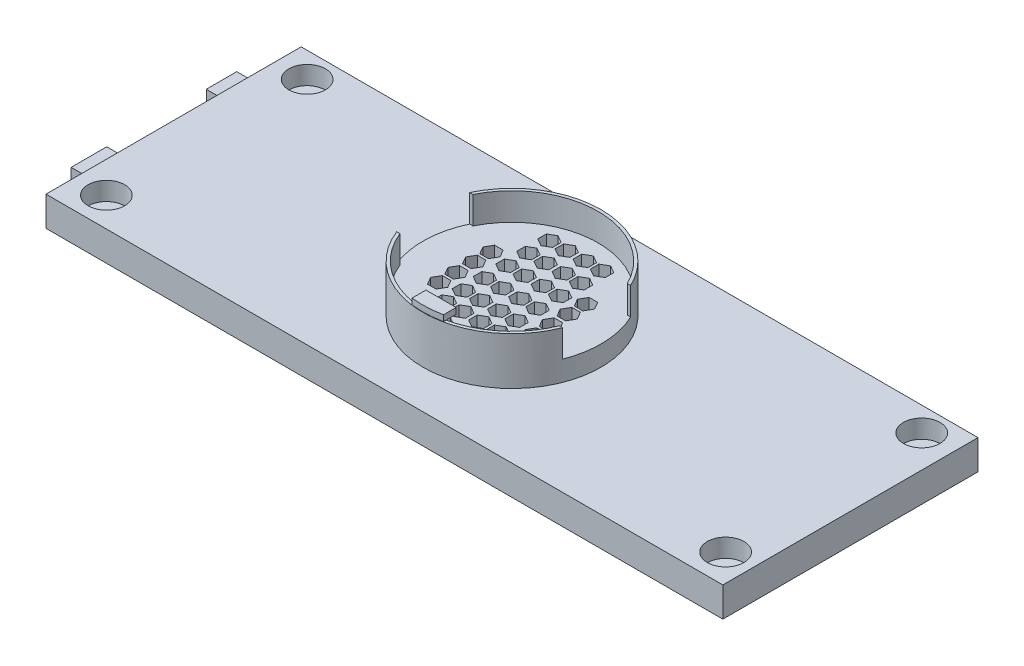
SolidWorks part; units mm, degrees
ref_plane "Front Plane" through (0, 0, 0) normal (0, 0, 1) x (1, 0, 0)
ref_plane "Top Plane" through (0, 0, 0) normal (0, 1, 0) x (1, 0, 0)
ref_plane "Right Plane" through (0, 0, 0) normal (1, 0, 0) x (0, 0, -1)
sketch "Sketch1" plane through (0, 0, 0) normal (0, 1, 0) x (1, 0, 0)
  line L1 (57, -21.4874) -> (-57, -21.4874)
  line L2 (57, -21.4874) -> (57, 21.4874)
  line L3 (57, 21.4874) -> (-57, 21.4874)
  line L4 (-57, -21.4874) -> (-57, 21.4874)
  line L5 (57, -21.4874) -> (-57, 21.4874) construction
  line L6 (57, 21.4874) -> (-57, -21.4874) construction
  point P0 (0, 0)
extrude "Boss-Extrude1" add sketch "Sketch1" along normal blind 5
sketch "Sketch2" plane through (0, 5, 0) normal (0, 1, 0) x (1, 0, 0)
  line L0 (-57, 21.4874) -> (-53.5, 21.4874) construction
  line L1 (57, 21.4874) -> (-57, 21.4874) construction
sketch "Sketch3" plane through (0, 5, 0) normal (0, 1, 0) x (1, 0, 0)
  line L0 (-51.7531, 23.5004) -> (-51.7531, -21.2397) construction
  line L1 (57.5677, 22.3499) -> (57.5677, -22.3902) construction
  line L2 (-55.25, 21.4874) -> (-55.25, -21.4874) construction
  line L3 (-57, 21.4874) -> (-53.5, 21.4874) construction
  line L4 (-57, -21.4874) -> (57, -21.4874) construction
  line L9 (-57, 0) -> (57, 0) construction
  line L10 (-57, 21.4874) -> (-57, -21.4874) construction
  line L11 (57, -21.4874) -> (57, 21.4874) construction
  line L12 (-51.7531, 17.2469) -> (51.585, 17.4252) construction
  line L13 (-0.0841, 17.3361) -> (-0.0841, -21.4874) construction
  line L14 (0, 0) -> (0, -21.4874) construction
  line L15 (-51.7531, -16.5649) -> (55.5178, -16.4581) construction
  line L16 (51.585, 17.4252) -> (52.4378, -16.4581) construction
  circle A0 centre (-51.7531, 17.2469) radius 3.08
  circle A1 centre (-51.7531, -16.5649) radius 3.08
  circle A2 centre (51.585, 17.4252) radius 3.08
  circle A3 centre (52.4378, -16.4581) radius 3.08
extrude "Cut-Extrude1" cut sketch "Sketch3" against normal blind 3.1
sketch "Sketch5" plane through (-57, 0, 0) normal (-1, 0, 0) x (0, 0, 1)
  line L0 (-22.3979, 2.4922) -> (22.3422, 2.4922) construction
  line L1 (-13.7478, 1.7003) -> (-13.7478, 3.7003)
  line L2 (-13.7478, 1.7003) -> (-8.6053, 1.7003)
  line L3 (-8.6053, 1.7003) -> (-8.6053, 3.7003)
  line L4 (-13.7478, 3.7003) -> (-8.6053, 3.7003)
  line L5 (-8.6053, 1.7003) -> (8.1572, 1.7003) construction
  line L9 (14.1572, 3.6937) -> (8.1572, 3.6937)
  line L10 (8.1572, 1.6901) -> (8.1572, 3.6937)
  line L11 (14.1572, 1.6901) -> (8.1572, 1.6901)
  line L12 (14.1572, 1.6901) -> (14.1572, 3.6937)
  line L13 (-21.4874, 2.5) -> (21.4874, 2.5) construction
  line L14 (-21.4874, 5) -> (-21.4874, 0) construction
  line L15 (21.4874, 5) -> (21.4874, 0) construction
  point P2 (-11.2129, 2.4922)
  point P11 (11.1572, 2.4922)
  dimension "D1" = 2
extrude "Boss-Extrude2" add sketch "Sketch5" along normal blind 3.1
sketch "Sketch6" plane through (0, 5, 0) normal (0, 1, 0) x (1, 0, 0)
  circle A0 centre (0, 0) radius 15
extrude "Boss-Extrude3" add sketch "Sketch6" along normal blind 8
sketch "Sketch8" plane through (0, 13, 0) normal (0, 1, 0) x (1, 0, 0)
  circle A0 centre (0, 0) radius 14.5
extrude "Cut-Extrude2" cut sketch "Sketch8" against normal blind 4.6
sketch "Sketch9" plane through (0, 8.4, 0) normal (0, 1, 0) x (1, 0, 0)
  line L0 (-18.3405, -5.4356) -> (20.9474, -5.4356)
  line L1 (20.9474, -5.4356) -> (20.9474, 6.4298)
  line L2 (20.9474, 6.4298) -> (-18.3405, 6.4298)
  line L3 (-18.3405, 6.4298) -> (-18.3405, -5.4356)
extrude "Cut-Extrude5" cut sketch "Sketch9" along normal blind 9.6
ref_plane "Plane1" through (13.9805, 13, 5.4356) normal (0.3624, 0, -0.932) x (-0.932, 0, -0.3624)
sketch "Sketch11" plane through (0, 13, 0) normal (0, 1, 0) x (1, 0, 0)
  line L0 (-2.0086, -12.4834) -> (-2.0086, -14.8138)
  line L1 (0, -12.4834) -> (-2.0086, -12.4834)
  line L3 (-2.0086, -12.4834) -> (3.0728, -12.4834)
  line L5 (3.0728, -12.4834) -> (3.0728, -14.6075)
  arc A3 (-2.0086, -14.8138) -> (3.0728, -14.6075) centre (-0.1027, 0.9217) ccw
extrude "Boss-Extrude5" add sketch "Sketch11" along normal blind 1 contours L3 L5 A3 L0
sketch "Sketch12" plane through (0, 0, 0) normal (0, -1, 0) x (1, 0, 0)
  line L0 (0, 14.5) -> (0, -14.5) construction
  line L1 (-15, 0) -> (15, 0) construction
  line L17 (-1.3814, -4.9711) -> (-0.1328, -4.2503)
  line L36 (-0.1328, -4.2503) -> (-0.1328, -2.8085)
  line L37 (-0.1328, -2.8085) -> (-1.3814, -2.0876)
  line L38 (-1.3814, -2.0876) -> (-2.63, -2.8085)
  line L39 (-2.63, -2.8085) -> (-2.63, -4.2503)
  line L40 (-2.63, -4.2503) -> (-1.3814, -4.9711)
  line L46 (-4.2896, -4.9711) -> (-3.041, -4.2503)
  line L47 (-3.041, -4.2503) -> (-3.041, -2.8085)
  line L48 (-3.041, -2.8085) -> (-4.2896, -2.0876)
  line L49 (-4.2896, -2.0876) -> (-5.5382, -2.8085)
  line L50 (-5.5382, -2.8085) -> (-5.5382, -4.2503)
  line L51 (-5.5382, -4.2503) -> (-4.2896, -4.9711)
  line L52 (4.5464, -5.001) -> (5.795, -4.2801)
  line L53 (5.795, -4.2801) -> (5.795, -2.8384)
  line L54 (5.795, -2.8384) -> (4.5464, -2.1175)
  line L55 (4.5464, -2.1175) -> (3.2978, -2.8384)
  line L56 (3.2978, -2.8384) -> (3.2978, -4.2801)
  line L57 (3.2978, -4.2801) -> (4.5464, -5.001)
  line L58 (1.6382, -5.001) -> (2.8868, -4.2801)
  line L59 (2.8868, -4.2801) -> (2.8868, -2.8384)
  line L60 (2.8868, -2.8384) -> (1.6382, -2.1175)
  line L61 (1.6382, -2.1175) -> (0.3896, -2.8384)
  line L62 (0.3896, -2.8384) -> (0.3896, -4.2801)
  line L63 (0.3896, -4.2801) -> (1.6382, -5.001)
  line L64 (-1.4428, -1.2342) -> (-0.1942, -0.5133)
  line L65 (-0.1942, -0.5133) -> (-0.1942, 0.9284)
  line L66 (-0.1942, 0.9284) -> (-1.4428, 1.6493)
  line L67 (-1.4428, 1.6493) -> (-2.6914, 0.9284)
  line L68 (-2.6914, 0.9284) -> (-2.6914, -0.5133)
  line L69 (-2.6914, -0.5133) -> (-1.4428, -1.2342)
  line L70 (-4.351, -1.2342) -> (-3.1025, -0.5133)
  line L71 (-3.1025, -0.5133) -> (-3.1025, 0.9284)
  line L72 (-3.1025, 0.9284) -> (-4.351, 1.6493)
  line L73 (-4.351, 1.6493) -> (-5.5996, 0.9284)
  line L74 (-5.5996, 0.9284) -> (-5.5996, -0.5133)
  line L75 (-5.5996, -0.5133) -> (-4.351, -1.2342)
  line L76 (4.4849, -1.2641) -> (5.7335, -0.5432)
  line L77 (5.7335, -0.5432) -> (5.7335, 0.8985)
  line L78 (5.7335, 0.8985) -> (4.4849, 1.6194)
  line L79 (4.4849, 1.6194) -> (3.2363, 0.8985)
  line L80 (3.2363, 0.8985) -> (3.2363, -0.5432)
  line L81 (3.2363, -0.5432) -> (4.4849, -1.2641)
  line L82 (1.5767, -1.2641) -> (2.8253, -0.5432)
  line L83 (2.8253, -0.5432) -> (2.8253, 0.8985)
  line L84 (2.8253, 0.8985) -> (1.5767, 1.6194)
  line L85 (1.5767, 1.6194) -> (0.3281, 0.8985)
  line L86 (0.3281, 0.8985) -> (0.3281, -0.5432)
  line L87 (0.3281, -0.5432) -> (1.5767, -1.2641)
  line L88 (-1.4428, 2.3085) -> (-0.1942, 3.0293)
  line L89 (-0.1942, 3.0293) -> (-0.1942, 4.4711)
  line L90 (-0.1942, 4.4711) -> (-1.4428, 5.192)
  line L91 (-1.4428, 5.192) -> (-2.6914, 4.4711)
  line L92 (-2.6914, 4.4711) -> (-2.6914, 3.0293)
  line L93 (-2.6914, 3.0293) -> (-1.4428, 2.3085)
  line L94 (-4.351, 2.3085) -> (-3.1025, 3.0293)
  line L95 (-3.1025, 3.0293) -> (-3.1025, 4.4711)
  line L96 (-3.1025, 4.4711) -> (-4.351, 5.192)
  line L97 (-4.351, 5.192) -> (-5.5996, 4.4711)
  line L98 (-5.5996, 4.4711) -> (-5.5996, 3.0293)
  line L99 (-5.5996, 3.0293) -> (-4.351, 2.3085)
  line L100 (4.4849, 2.2786) -> (5.7335, 2.9995)
  line L101 (5.7335, 2.9995) -> (5.7335, 4.4412)
  line L102 (5.7335, 4.4412) -> (4.4849, 5.1621)
  line L103 (4.4849, 5.1621) -> (3.2363, 4.4412)
  line L104 (3.2363, 4.4412) -> (3.2363, 2.9995)
  line L105 (3.2363, 2.9995) -> (4.4849, 2.2786)
  line L106 (1.5767, 2.2786) -> (2.8253, 2.9995)
  line L107 (2.8253, 2.9995) -> (2.8253, 4.4412)
  line L108 (2.8253, 4.4412) -> (1.5767, 5.1621)
  line L109 (1.5767, 5.1621) -> (0.3281, 4.4412)
  line L110 (0.3281, 4.4412) -> (0.3281, 2.9995)
  line L111 (0.3281, 2.9995) -> (1.5767, 2.2786)
  line L112 (-1.4248, 5.5165) -> (-0.1763, 6.2374)
  line L113 (-0.1763, 6.2374) -> (-0.1763, 7.6792)
  line L114 (-0.1763, 7.6792) -> (-1.4248, 8.4)
  line L115 (-1.4248, 8.4) -> (-2.6734, 7.6792)
  line L116 (-2.6734, 7.6792) -> (-2.6734, 6.2374)
  line L117 (-2.6734, 6.2374) -> (-1.4248, 5.5165)
  line L118 (-4.3331, 5.5165) -> (-3.0845, 6.2374)
  line L119 (-3.0845, 6.2374) -> (-3.0845, 7.6792)
  line L120 (-3.0845, 7.6792) -> (-4.3331, 8.4)
  line L121 (-4.3331, 8.4) -> (-5.5816, 7.6792)
  line L122 (-5.5816, 7.6792) -> (-5.5816, 6.2374)
  line L123 (-5.5816, 6.2374) -> (-4.3331, 5.5165)
  line L124 (4.5029, 5.4867) -> (5.7515, 6.2075)
  line L125 (5.7515, 6.2075) -> (5.7515, 7.6493)
  line L126 (5.7515, 7.6493) -> (4.5029, 8.3702)
  line L127 (4.5029, 8.3702) -> (3.2543, 7.6493)
  line L128 (3.2543, 7.6493) -> (3.2543, 6.2075)
  line L129 (3.2543, 6.2075) -> (4.5029, 5.4867)
  line L130 (1.5947, 5.4867) -> (2.8433, 6.2075)
  line L131 (2.8433, 6.2075) -> (2.8433, 7.6493)
  line L132 (2.8433, 7.6493) -> (1.5947, 8.3702)
  line L133 (1.5947, 8.3702) -> (0.3461, 7.6493)
  line L134 (0.3461, 7.6493) -> (0.3461, 6.2075)
  line L135 (0.3461, 6.2075) -> (1.5947, 5.4867)
  line L136 (-1.4064, 8.9229) -> (-0.1579, 9.6438)
  line L137 (-0.1579, 9.6438) -> (-0.1579, 11.0856)
  line L138 (-0.1579, 11.0856) -> (-1.4064, 11.8064)
  line L139 (-1.4064, 11.8064) -> (-2.655, 11.0856)
  line L140 (-2.655, 11.0856) -> (-2.655, 9.6438)
  line L141 (-2.655, 9.6438) -> (-1.4064, 8.9229)
  line L142 (-4.3147, 8.9229) -> (-3.0661, 9.6438)
  line L143 (-3.0661, 9.6438) -> (-3.0661, 11.0856)
  line L144 (-3.0661, 11.0856) -> (-4.3147, 11.8064)
  line L145 (-4.3147, 11.8064) -> (-5.5633, 11.0856)
  line L146 (-5.5633, 11.0856) -> (-5.5633, 9.6438)
  line L147 (-5.5633, 9.6438) -> (-4.3147, 8.9229)
  line L148 (4.5213, 8.8931) -> (5.7699, 9.6139)
  line L149 (5.7699, 9.6139) -> (5.7699, 11.0557)
  line L150 (5.7699, 11.0557) -> (4.5213, 11.7766)
  line L151 (4.5213, 11.7766) -> (3.2727, 11.0557)
  line L152 (3.2727, 11.0557) -> (3.2727, 9.6139)
  line L153 (3.2727, 9.6139) -> (4.5213, 8.8931)
  line L154 (1.6131, 8.8931) -> (2.8617, 9.6139)
  line L155 (2.8617, 9.6139) -> (2.8617, 11.0557)
  line L156 (2.8617, 11.0557) -> (1.6131, 11.7766)
  line L157 (1.6131, 11.7766) -> (0.3645, 11.0557)
  line L158 (0.3645, 11.0557) -> (0.3645, 9.6139)
  line L159 (0.3645, 9.6139) -> (1.6131, 8.8931)
  line L160 (-1.4667, -8.5789) -> (-0.2181, -7.858)
  line L161 (-0.2181, -7.858) -> (-0.2181, -6.4163)
  line L162 (-0.2181, -6.4163) -> (-1.4667, -5.6954)
  line L163 (-1.4667, -5.6954) -> (-2.7153, -6.4163)
  line L164 (-2.7153, -6.4163) -> (-2.7153, -7.858)
  line L165 (-2.7153, -7.858) -> (-1.4667, -8.5789)
  line L166 (-4.3749, -8.5789) -> (-3.1263, -7.858)
  line L167 (-3.1263, -7.858) -> (-3.1263, -6.4163)
  line L168 (-3.1263, -6.4163) -> (-4.3749, -5.6954)
  line L169 (-4.3749, -5.6954) -> (-5.6235, -6.4163)
  line L170 (-5.6235, -6.4163) -> (-5.6235, -7.858)
  line L171 (-5.6235, -7.858) -> (-4.3749, -8.5789)
  line L172 (4.461, -8.6088) -> (5.7096, -7.8879)
  line L173 (5.7096, -7.8879) -> (5.7096, -6.4461)
  line L174 (5.7096, -6.4461) -> (4.461, -5.7253)
  line L175 (4.461, -5.7253) -> (3.2124, -6.4461)
  line L176 (3.2124, -6.4461) -> (3.2124, -7.8879)
  line L177 (3.2124, -7.8879) -> (4.461, -8.6088)
  line L178 (1.5528, -8.6088) -> (2.8014, -7.8879)
  line L179 (2.8014, -7.8879) -> (2.8014, -6.4461)
  line L180 (2.8014, -6.4461) -> (1.5528, -5.7253)
  line L181 (1.5528, -5.7253) -> (0.3042, -6.4461)
  line L182 (0.3042, -6.4461) -> (0.3042, -7.8879)
  line L183 (0.3042, -7.8879) -> (1.5528, -8.6088)
  line L184 (-1.5025, -12.1629) -> (-0.2539, -11.442)
  line L185 (-0.2539, -11.442) -> (-0.2539, -10.0003)
  line L186 (-0.2539, -10.0003) -> (-1.5025, -9.2794)
  line L187 (-1.5025, -9.2794) -> (-2.7511, -10.0003)
  line L188 (-2.7511, -10.0003) -> (-2.7511, -11.442)
  line L189 (-2.7511, -11.442) -> (-1.5025, -12.1629)
  line L190 (-4.4107, -12.1629) -> (-3.1621, -11.442)
  line L191 (-3.1621, -11.442) -> (-3.1621, -10.0003)
  line L192 (-3.1621, -10.0003) -> (-4.4107, -9.2794)
  line L193 (-4.4107, -9.2794) -> (-5.6593, -10.0003)
  line L194 (-5.6593, -10.0003) -> (-5.6593, -11.442)
  line L195 (-5.6593, -11.442) -> (-4.4107, -12.1629)
  line L196 (4.4253, -12.1928) -> (5.6739, -11.4719)
  line L197 (5.6739, -11.4719) -> (5.6739, -10.0301)
  line L198 (5.6739, -10.0301) -> (4.4253, -9.3093)
  line L199 (4.4253, -9.3093) -> (3.1767, -10.0301)
  line L200 (3.1767, -10.0301) -> (3.1767, -11.4719)
  line L201 (3.1767, -11.4719) -> (4.4253, -12.1928)
  line L202 (1.5171, -12.1928) -> (2.7657, -11.4719)
  line L203 (2.7657, -11.4719) -> (2.7657, -10.0301)
  line L204 (2.7657, -10.0301) -> (1.5171, -9.3093)
  line L205 (1.5171, -9.3093) -> (0.2685, -10.0301)
  line L206 (0.2685, -10.0301) -> (0.2685, -11.4719)
  line L207 (0.2685, -11.4719) -> (1.5171, -12.1928)
  line L208 (-6.2102, -1.2905) -> (-6.9311, -0.0419)
  line L209 (-6.9311, -0.0419) -> (-8.3728, -0.0419)
  line L210 (-8.3728, -0.0419) -> (-9.0937, -1.2905)
  line L211 (-9.0937, -1.2905) -> (-8.3728, -2.539)
  line L212 (-8.3728, -2.539) -> (-6.9311, -2.539)
  line L213 (-6.9311, -2.539) -> (-6.2102, -1.2905)
  line L214 (-6.2102, -4.1987) -> (-6.9311, -2.9501)
  line L215 (-6.9311, -2.9501) -> (-8.3728, -2.9501)
  line L216 (-8.3728, -2.9501) -> (-9.0937, -4.1987)
  line L217 (-9.0937, -4.1987) -> (-8.3728, -5.4473)
  line L218 (-8.3728, -5.4473) -> (-6.9311, -5.4473)
  line L219 (-6.9311, -5.4473) -> (-6.2102, -4.1987)
  line L220 (-6.1803, 4.6373) -> (-6.9012, 5.8859)
  line L221 (-6.9012, 5.8859) -> (-8.3429, 5.8859)
  line L222 (-8.3429, 5.8859) -> (-9.0638, 4.6373)
  line L223 (-9.0638, 4.6373) -> (-8.3429, 3.3887)
  line L224 (-8.3429, 3.3887) -> (-6.9012, 3.3887)
  line L225 (-6.9012, 3.3887) -> (-6.1803, 4.6373)
  line L226 (-6.1803, 1.7291) -> (-6.9012, 2.9777)
  line L227 (-6.9012, 2.9777) -> (-8.3429, 2.9777)
  line L228 (-8.3429, 2.9777) -> (-9.0638, 1.7291)
  line L229 (-9.0638, 1.7291) -> (-8.3429, 0.4805)
  line L230 (-8.3429, 0.4805) -> (-6.9012, 0.4805)
  line L231 (-6.9012, 0.4805) -> (-6.1803, 1.7291)
  line L232 (9.3641, -1.6319) -> (8.6432, -0.3833)
  line L233 (8.6432, -0.3833) -> (7.2014, -0.3833)
  line L234 (7.2014, -0.3833) -> (6.4806, -1.6319)
  line L235 (6.4806, -1.6319) -> (7.2014, -2.8804)
  line L236 (7.2014, -2.8804) -> (8.6432, -2.8804)
  line L237 (8.6432, -2.8804) -> (9.3641, -1.6319)
  line L238 (9.3641, -4.5401) -> (8.6432, -3.2915)
  line L239 (8.6432, -3.2915) -> (7.2014, -3.2915)
  line L240 (7.2014, -3.2915) -> (6.4806, -4.5401)
  line L241 (6.4806, -4.5401) -> (7.2014, -5.7887)
  line L242 (7.2014, -5.7887) -> (8.6432, -5.7887)
  line L243 (8.6432, -5.7887) -> (9.3641, -4.5401)
  line L244 (9.3939, 4.2959) -> (8.6731, 5.5445)
  line L245 (8.6731, 5.5445) -> (7.2313, 5.5445)
  line L246 (7.2313, 5.5445) -> (6.5104, 4.2959)
  line L247 (6.5104, 4.2959) -> (7.2313, 3.0473)
  line L248 (7.2313, 3.0473) -> (8.6731, 3.0473)
  line L249 (8.6731, 3.0473) -> (9.3939, 4.2959)
  line L250 (9.3939, 1.3877) -> (8.6731, 2.6363)
  line L251 (8.6731, 2.6363) -> (7.2313, 2.6363)
  line L252 (7.2313, 2.6363) -> (6.5104, 1.3877)
  line L253 (6.5104, 1.3877) -> (7.2313, 0.1391)
  line L254 (7.2313, 0.1391) -> (8.6731, 0.1391)
  line L255 (8.6731, 0.1391) -> (9.3939, 1.3877)
  circle A0 centre (-1.4248, 6.9583) radius 1.2486 construction
  circle A12 centre (-1.3814, -3.5294) radius 1.2486 construction
  circle A14 centre (-4.2896, -3.5294) radius 1.2486 construction
  circle A15 centre (4.5464, -3.5593) radius 1.2486 construction
  circle A16 centre (1.6382, -3.5593) radius 1.2486 construction
  circle A17 centre (-1.4428, 0.2075) radius 1.2486 construction
  circle A18 centre (-4.351, 0.2075) radius 1.2486 construction
  circle A19 centre (4.4849, 0.1777) radius 1.2486 construction
  circle A20 centre (1.5767, 0.1777) radius 1.2486 construction
  circle A21 centre (-1.4428, 3.7502) radius 1.2486 construction
  circle A22 centre (-4.351, 3.7502) radius 1.2486 construction
  circle A23 centre (4.4849, 3.7203) radius 1.2486 construction
  circle A24 centre (1.5767, 3.7203) radius 1.2486 construction
  circle A25 centre (-4.3331, 6.9583) radius 1.2486 construction
  circle A26 centre (4.5029, 6.9284) radius 1.2486 construction
  circle A27 centre (1.5947, 6.9284) radius 1.2486 construction
  circle A28 centre (-1.4064, 10.3647) radius 1.2486 construction
  circle A29 centre (-4.3147, 10.3647) radius 1.2486 construction
  circle A30 centre (4.5213, 10.3348) radius 1.2486 construction
  circle A31 centre (1.6131, 10.3348) radius 1.2486 construction
  circle A32 centre (-1.4667, -7.1372) radius 1.2486 construction
  circle A33 centre (-4.3749, -7.1372) radius 1.2486 construction
  circle A34 centre (4.461, -7.167) radius 1.2486 construction
  circle A35 centre (1.5528, -7.167) radius 1.2486 construction
  circle A36 centre (-1.5025, -10.7211) radius 1.2486 construction
  circle A37 centre (-4.4107, -10.7211) radius 1.2486 construction
  circle A38 centre (4.4253, -10.751) radius 1.2486 construction
  circle A39 centre (1.5171, -10.751) radius 1.2486 construction
  circle A40 centre (-7.6519, -1.2905) radius 1.2486 construction
  circle A41 centre (-7.6519, -4.1987) radius 1.2486 construction
  circle A42 centre (-7.6221, 4.6373) radius 1.2486 construction
  circle A43 centre (-7.6221, 1.7291) radius 1.2486 construction
  circle A44 centre (7.9223, -1.6319) radius 1.2486 construction
  circle A45 centre (7.9223, -4.5401) radius 1.2486 construction
  circle A46 centre (7.9522, 4.2959) radius 1.2486 construction
  circle A47 centre (7.9522, 1.3877) radius 1.2486 construction
extrude "Cut-Extrude6" cut sketch "Sketch12" against normal blind 10
